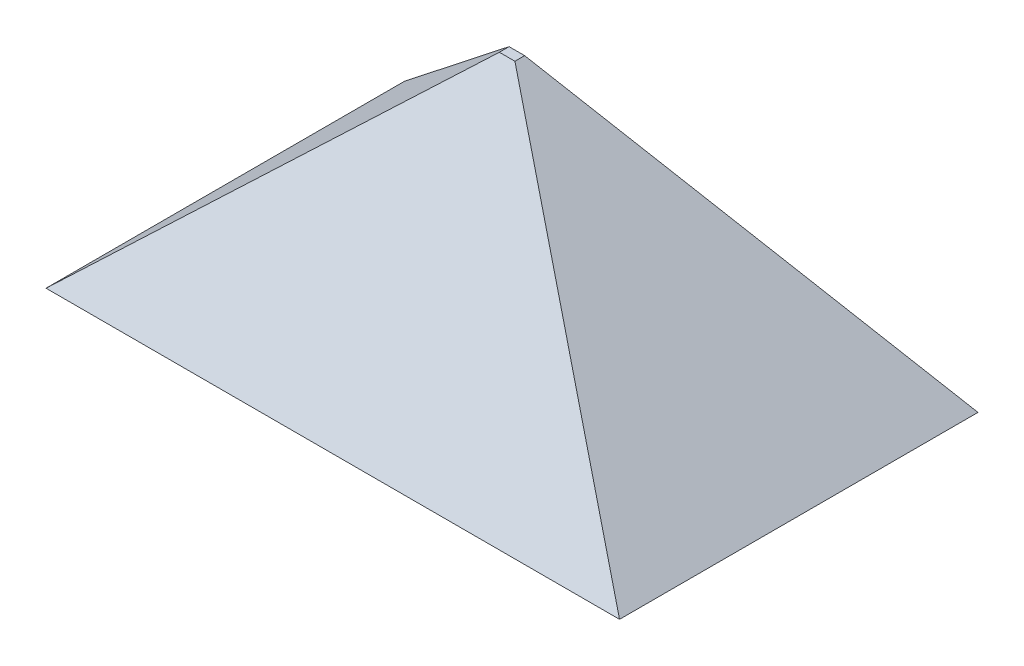
SolidWorks part; units mm, degrees
ref_plane "Front Plane" through (0, 0, 0) normal (0, 0, 1) x (1, 0, 0)
ref_plane "Top Plane" through (0, 0, 0) normal (0, 1, 0) x (1, 0, 0)
ref_plane "Right Plane" through (0, 0, 0) normal (1, 0, 0) x (0, 0, -1)
ref_plane "distance of measurement" through (0, 90.932, 0) normal (0, 1, 0) x (1, 0, 0)
sketch "Sketch1" plane through (0, 0, 0) normal (0, 1, 0) x (1, 0, 0)
  line L1 (-101.6, -63.5) -> (101.6, -63.5)
  line L2 (-101.6, -63.5) -> (-101.6, 63.5)
  line L3 (-101.6, 63.5) -> (101.6, 63.5)
  line L4 (101.6, -63.5) -> (101.6, 63.5)
  line L5 (-101.6, -63.5) -> (101.6, 63.5) construction
  line L6 (-101.6, 63.5) -> (101.6, -63.5) construction
  point P0 (0, 0)
sketch "Sketch2" plane through (0, 90.932, 0) normal (0, 1, 0) x (1, 0, 0)
  line L0 (-101.6, -63.5) -> (101.6, 63.5) construction
  line L1 (-2.7554, -1.7221) -> (2.7554, -1.7221)
  line L2 (-2.7554, -1.7221) -> (-2.7554, 1.7221)
  line L3 (-2.7554, 1.7221) -> (2.7554, 1.7221)
  line L4 (2.7554, -1.7221) -> (2.7554, 1.7221)
  line L5 (-2.7554, -1.7221) -> (2.7554, 1.7221) construction
  line L6 (-2.7554, 1.7221) -> (2.7554, -1.7221) construction
  point P0 (0, 0)
loft "FOV" add profiles "Sketch2", "Sketch1" connector at (-2.7554, 90.932, 1.7221) connector at (-101.6, 0, 63.5)
